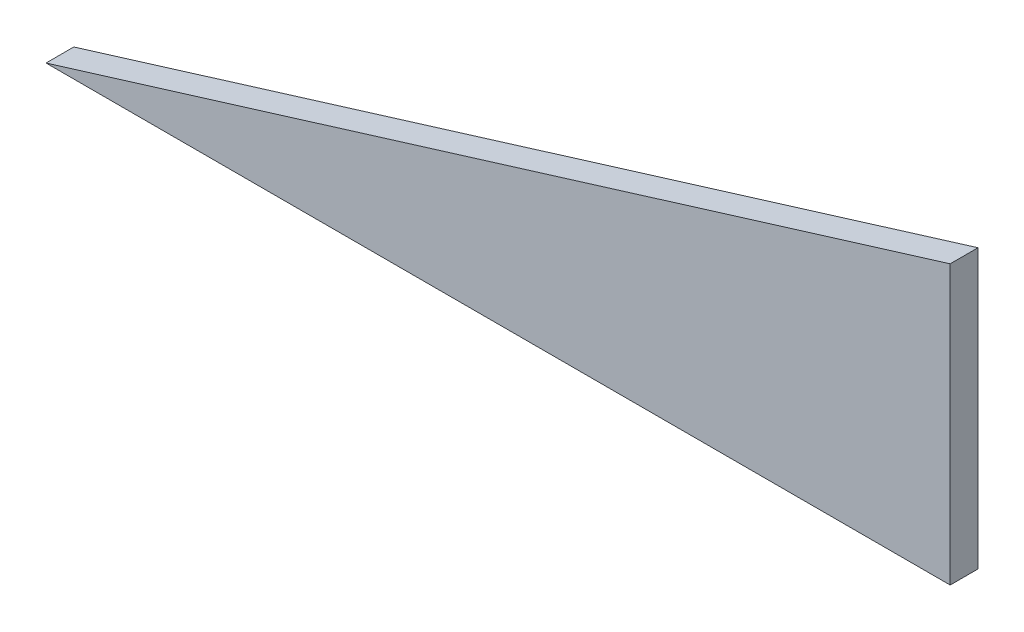
SolidWorks part; units mm, degrees
ref_plane "Ön Düzlem" through (0, 0, 0) normal (0, 0, 1) x (1, 0, 0)
ref_plane "Üst Düzlem" through (0, 0, 0) normal (0, 1, 0) x (1, 0, 0)
ref_plane "Sağ Düzlem" through (0, 0, 0) normal (1, 0, 0) x (0, 0, -1)
sketch "Çizim1" plane through (0, 0, 0) normal (0, 0, 1) x (1, 0, 0)
  line L0 (0, 0) -> (-260, 0)
  line L1 (-260, 0) -> (0, 80)
  line L2 (0, 80) -> (0, 0)
  dimension "D1" = 80
  dimension "D2" = 260
base flange "Taban-Flanş1" sketch "Çizim1" thickness 8 reverse thickness direction no parameters "D1"=8
sketch "Büküm-Çizgileri1" [suppressed] plane through (0, 0, 0) normal (0, 1, 0) x (1, 0, 0)
sketch "Sınırlandırma-Kutusu1" [suppressed] plane through (0, 0, 0) normal (0, 1, 0) x (1, 0, 0)
sheet metal parameters "Sac-Levha1" thickness 8 parameters "D1"=8
flat pattern "Düz-Çoğaltma1" [suppressed]
sketch "Büküm-Çizgileri2" plane through (0, 0, 0) normal (0, 1, 0) x (1, 0, 0)
sketch3d "Sınırlandırma-Kutusu2" [suppressed]
  line L0 (-260, 0, 0) -> (0, 0, 0) construction
  line L1 (-260, 80, 0) -> (0, 80, 0) construction
  line L2 (-260, 0, 0) -> (-260, 80, 0) construction
  line L3 (0, 0, 0) -> (0, 80, 0) construction
